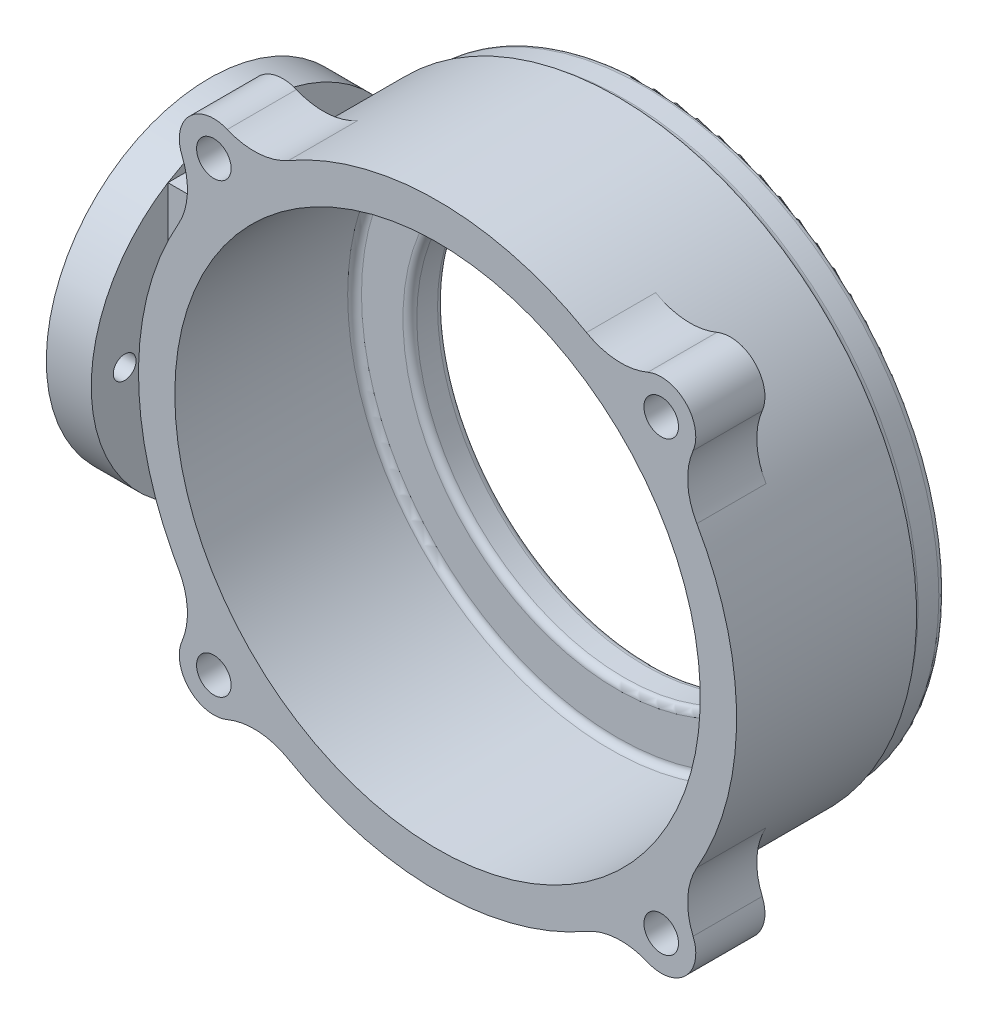
SolidWorks part; units mm, degrees
material "6061 Alloy"
ref_plane "Front Plane" through (0, 0, 0) normal (0, 0, 1) x (1, 0, 0)
ref_plane "Top Plane" through (0, 0, 0) normal (0, 1, 0) x (1, 0, 0)
ref_plane "Right Plane" through (0, 0, 0) normal (1, 0, 0) x (0, 0, -1)
sketch "Sketch1" plane through (0, 0, 0) normal (0, 0, 1) x (1, 0, 0)
  line L0 (0, 0) -> (-45, 0) construction
  line L4 (0, 43.25) -> (-45, 43.25) construction
  line L5 (-45, 43.25) -> (-45, -43.25) construction
  line L6 (0, -43.25) -> (-45, -43.25) construction
  line L7 (-38.3479, 20) -> (-45, 20)
  line L8 (-45, 20) -> (-45, -20)
  line L9 (-38.3479, -20) -> (-45, -20)
  circle A0 centre (0, 0) radius 38
  arc A1 (0, -43.25) -> (0, 43.25) centre (0, 0) ccw construction
  arc A2 (-38.3479, -20) -> (-38.3479, 20) centre (0, 0) ccw
  dimension "D1" = 76
  dimension "D2" = 43.25
  dimension "D4" = 40
  dimension "D3" = 45
extrude "Boss-Extrude1" add sketch "Sketch1" along normal blind 40
sketch "Sketch6" plane through (0, 0, 0) normal (0, 0, -1) x (-1, 0, 0)
  circle A0 centre (0, 0) radius 99.6758
extrude "Cut-Extrude3" cut sketch "Sketch6" against normal mid plane 40
sketch "Sketch7" plane through (0, 0, 20) normal (0, 0, 1) x (1, 0, 0)
  circle A1 centre (0, 0) radius 42.5
  circle A2 centre (0, 0) radius 30
  dimension "D1" = 60
  dimension "D2" = 85
extrude "Boss-Extrude4" add sketch "Sketch7" against normal blind 5
fillet "Fillet1" radius 1 5 edges at (42.5, 0, 15) (30, 0, 15) (-38, 0, 20) (30, 0, 20) (42.5, 0, 20)
sketch "Sketch8" plane through (-45, 0, 0) normal (-1, 0, 0) x (0, 0, 1)
  line L0 (27.5, 0) -> (27.5, 18.75) construction
  line L7 (27.5, 0) -> (46.25, 0) construction
  line L10 (15, 0) -> (40, 0) construction
  line L11 (15, 41.5) -> (15, -41.5) construction
  line L12 (40, 0) -> (15, 0) construction
  line L13 (27.5, 0) -> (27.5, 43.25) construction
  line L14 (40, 20) -> (40, -20) construction
  arc A13 (22.5046, -0.2152) -> (22.504, -0.1987) centre (27.5, 0) ccw construction
  arc A14 (22.504, -0.1987) -> (22.5046, -0.2152) centre (27.5, 0) ccw construction
  arc A15 (25.8502, 18.7248) -> (25.8502, 18.7215) centre (27.5, 18.75) ccw construction
  circle A31 centre (27.5, 18.75) radius 1.65
  circle A32 centre (27.5, 0) radius 5
  circle A33 centre (46.25, 0) radius 1.65
  circle A34 centre (27.5, -18.75) radius 1.65
  circle A35 centre (8.75, 0) radius 1.65
  circle A37 centre (27.5, 0) radius 23.585
  point P26 (0, 0)
  point P29 (27.5, 0)
  point P37 (-17.5, 0)
  dimension "D5" = 18.75
  dimension "D4" = 3.3
  dimension "D6" = 10
  dimension "D7" = 4
extrude "Boss-Extrude5" add sketch "Sketch8" along normal blind 6.5
ref_axis "Axis1" through (0, 0, 40) along (0, 0, -1)
sketch "Sketch9" plane through (0, 0, 0) normal (0, 1, 0) x (1, 0, 0)
  line L0 (0, -40) -> (0, -46) construction
  line L1 (0, -40) -> (0, -21) construction
  line L2 (0, -46) -> (42.5, -46) construction
  line L3 (42.5, -46) -> (42.5, -17.5) construction
  line L4 (42.5, -19) -> (42.5, -16) construction
  line L9 (-38.3479, -40) -> (43.25, -40) construction
  line L10 (38, -40) -> (38, -46)
  line L11 (43.25, -40) -> (43.25, -19.9682) construction
  line L12 (38, -40) -> (43.25, -40)
  line L14 (43.25, -40) -> (43.25, -46)
  line L15 (43.25, -46) -> (42.5, -46)
  line L17 (42.5, -46) -> (38, -46)
  dimension "D1" = 5.25
  dimension "D2" = 6
revolve "Revolve1" add sketch "Sketch9" angle 360 about L0
sketch "Sketch10" plane through (0, 0, 46) normal (0, 0, 1) x (1, 0, 0)
  line L0 (0, 0) -> (-32.3501, 32.3501) construction
  line L1 (-38.3479, 20) -> (-45, 20) construction
  line L2 (0, 0) -> (32.3501, 32.3501) construction
  line L3 (0, 0) -> (32.3501, -32.3501) construction
  line L4 (0, 0) -> (-32.3501, -32.3501) construction
  circle A2 centre (-32.3501, 32.3501) radius 2.5
  circle A3 centre (0, 0) radius 43.25 construction
  arc A7 (-27.3533, 32.5276) -> (-32.5276, 27.3533) centre (-32.3501, 32.3501) ccw
  arc A10 (-27.3533, 32.5276) -> (-32.5276, 27.3533) centre (0, 0) ccw
  circle A11 centre (32.3501, 32.3501) radius 2.5 [skipped]
  circle A12 centre (32.3501, -32.3501) radius 2.5 [skipped]
  circle A13 centre (-32.3501, -32.3501) radius 2.5 [skipped]
  circle A15 centre (32.3501, 32.3501) radius 2.5
  arc A16 (32.5276, 27.3533) -> (27.3533, 32.5276) centre (32.3501, 32.3501) ccw
  arc A17 (32.5276, 27.3533) -> (27.3533, 32.5276) centre (0, 0) ccw
  circle A18 centre (32.3501, -32.3501) radius 2.5
  arc A19 (27.3533, -32.5276) -> (32.5276, -27.3533) centre (32.3501, -32.3501) ccw
  arc A20 (27.3533, -32.5276) -> (32.5276, -27.3533) centre (0, 0) ccw
  circle A21 centre (-32.3501, -32.3501) radius 2.5
  arc A22 (-32.5276, -27.3533) -> (-27.3533, -32.5276) centre (-32.3501, -32.3501) ccw
  arc A23 (-32.5276, -27.3533) -> (-27.3533, -32.5276) centre (0, 0) ccw
  point P18 (0, 0)
  point P35 (0, 0)
  dimension "D1" = 45
  dimension "D2" = 5
  dimension "D4" = 10
  dimension "D6" = 42.5
  dimension "D3" = 4
  dimension "D5" = 4
extrude "Boss-Extrude6" add sketch "Sketch10" against normal blind 10
fillet "Fillet2" radius 10 8 edges at (-27.464, 33.411, 41) (-33.411, 27.464, 41) (27.464, 33.411, 41) (33.411, 27.464, 41) (-33.411, -27.464, 41) (-27.464, -33.411, 41) (27.464, -33.411, 41) (33.411, -27.464, 41)
